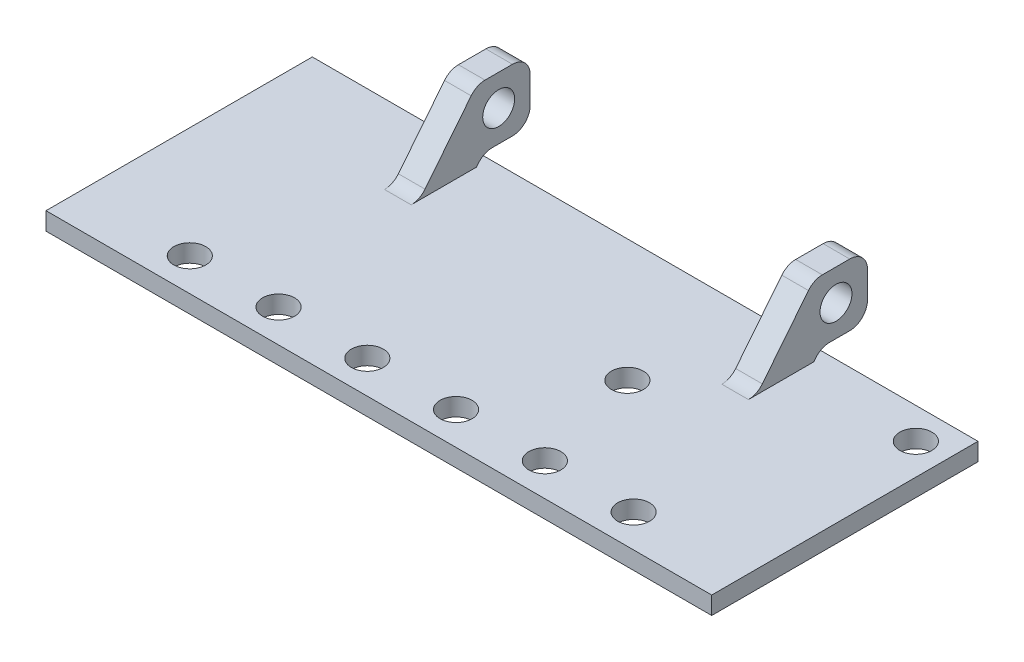
SolidWorks part; units mm, degrees
ref_plane "Front Plane" through (0, 0, 0) normal (0, 0, 1) x (1, 0, 0)
ref_plane "Top Plane" through (0, 0, 0) normal (0, 1, 0) x (1, 0, 0)
ref_plane "Right Plane" through (0, 0, 0) normal (1, 0, 0) x (0, 0, -1)
sketch "Sketch1" plane through (0, 0, 0) normal (0, 1, 0) x (1, 0, 0)
  line L0 (37.5, 0) -> (37.5, 30) construction
  line L1 (0, 0) -> (75, 0)
  line L2 (0, 0) -> (0, 30)
  line L3 (0, 30) -> (75, 30)
  line L4 (75, 0) -> (75, 30)
  dimension "D1" = 75
  dimension "D2" = 30
extrude "Boss-Extrude1" add sketch "Sketch1" along normal blind 2
hole_wizard "M3 Clearance Hole1" positions "Sketch2" profile "Sketch3" hole size "M3" standard "ANSI Metric" end condition through all
sketch "Sketch2" plane through (0, 2, 0) normal (0, 1, 0) x (1, 0, 0)
  line L0 (37.5, 30) -> (37.5, 0) construction
  line L1 (75, 30) -> (0, 30) construction
  line L2 (0, 0) -> (75, 0) construction
  point P9 (32.5, 3.7)
  point P17 (22.5, 3.7)
  point P18 (12.5, 3.7)
  point P19 (62.5, 3.7)
  point P20 (52.5, 3.7)
  point P21 (42.5, 3.7)
  dimension "D1" = 5
  dimension "D2" = 3.7
  dimension "D4" = 10
  dimension "D3" = 3
sketch "Sketch3" plane through (42.5, 2, -3.7) normal (1, 0, 0) x (0, 0, 1)
  line L0 (0, 0) -> (0, 2)
  line L1 (0, 2) -> (1.8, 2)
  line L2 (1.8, 2) -> (1.8, 0)
  line L5 (1.8, 0) -> (0, 0)
  line L11 (0, -6.35) -> (0, 107.95) construction
  dimension "Thru Hole Dia." = 3.6
  dimension "Thru Hole Depth" = 2
ref_plane "Plane1" through (20, 0, 0) normal (-1, 0, 0) x (0, 0, 1)
sketch "Sketch4" plane through (20, 0, 0) normal (-1, 0, 0) x (0, 0, 1)
  line L0 (-28.5, 2) -> (-28.7065, 2.2585)
  line L1 (-30.269, 3.01) -> (-32.55, 3.01)
  line L2 (-34.55, 5.01) -> (-34.55, 8.01)
  line L3 (-32.55, 10.01) -> (-29.462, 10.01)
  line L4 (-27.8995, 9.2585) -> (-22.1, 2)
  line L5 (-30, 2) -> (0, 2) construction
  line L7 (-28.5, 2) -> (-22.1, 2)
  line L10 (-30, 2) -> (-30, 0) construction
  circle A0 centre (-31, 6.51) radius 1.75
  arc A1 (-34.55, 8.01) -> (-32.55, 10.01) centre (-32.55, 8.01) cw
  arc A2 (-32.55, 3.01) -> (-34.55, 5.01) centre (-32.55, 5.01) cw
  arc A3 (-28.7065, 2.2585) -> (-30.269, 3.01) centre (-30.269, 1.01) ccw
  arc A4 (-29.462, 10.01) -> (-27.8995, 9.2585) centre (-29.462, 8.01) cw
  point P2 (0, 0)
  point P11 (0, 0)
  point P12 (-34.55, 6.51)
  point P13 (0, 0)
  point P26 (-28.5, 10.01)
  dimension "D1" = 3.5
  dimension "D5" = 2
  dimension "D7" = 2
  dimension "D2" = 7
  dimension "D3" = 3.55
  dimension "D4" = 1.5
  dimension "D6" = 5
  dimension "D8" = 6.4
  dimension "D9" = 2.5
ref_plane "Plane2" through (55, 0, 0) normal (1, 0, 0) x (0, 0, -1)
extrude "Boss-Extrude2" add sketch "Sketch4" along normal blind 3 contours A4 L3 A1 L2 A2 L1 A3 L0 L7 L4 A0 | A0 region at (20, 5.6399, -29.2006) region at (20, 6.51, -31)
extrude "Boss-Extrude3" add sketch "Sketch4<2>" against normal blind 3 from surface contours A0 | A4 L3 A1 L2 A2 L1 A3 L0 L7 L4 A0 region at (20, 5.6399, -29.2006) region at (20, 6.51, -31) starting at plane "Plane2"
sketch "Sketch4<2>" plane through (20, 0, 0) normal (-1, 0, 0) x (0, 0, 1) same geometry as "Sketch4"
fillet "Fillet1" radius 2 2 edges at (18.5, 2, -22.1) (56.5, 2, -22.1)
hole_wizard "M3 Clearance Hole2" positions "Sketch5" profile "Sketch6" hole size "M3" standard "ANSI Metric" end condition through all
sketch "Sketch5" plane through (58, 0, 0) normal (1, 0, 0) x (0, 0, -1)
  point P5 (31, 6.51)
sketch "Sketch6" plane through (58, 6.51, -31) normal (0, 1, 0) x (0, 0, -1)
  line L0 (0, 0) -> (0, 58)
  line L1 (0, 58) -> (1.8, 58)
  line L2 (1.8, 58) -> (1.8, 0)
  line L5 (1.8, 0) -> (0, 0)
  line L11 (0, -6.35) -> (0, 107.95) construction
  dimension "Thru Hole Dia." = 3.6
  dimension "Thru Hole Depth" = 58
hole_wizard "M3 Clearance Hole3" positions "Sketch7" profile "Sketch8" hole size "M3" standard "ANSI Metric" end condition through all
sketch "Sketch7" plane through (0, 0, 0) normal (0, -1, 0) x (-1, 0, 0)
  line L0 (-75, 0) -> (-75, 30) construction
  line L1 (-75, 30) -> (0, 30) construction
  point P0 (-49.3, 16.2)
  point P3 (-71.5, 26.5)
  point P6 (0, 0)
  point P7 (0, 0)
  point P8 (0, 0)
  dimension "D1" = 22.2
  dimension "D2" = 10.3
  dimension "D3" = 3.5
  dimension "D4" = 3.5
sketch "Sketch8" plane through (49.3, 0, -16.2) normal (1, 0, 0) x (0, 0, -1)
  line L0 (0, 0) -> (0, 10.01)
  line L1 (0, 10.01) -> (1.8, 10.01)
  line L2 (1.8, 10.01) -> (1.8, 0)
  line L5 (1.8, 0) -> (0, 0)
  line L11 (0, -6.35) -> (0, 107.95) construction
  dimension "Thru Hole Dia." = 3.6
  dimension "Thru Hole Depth" = 10.01
